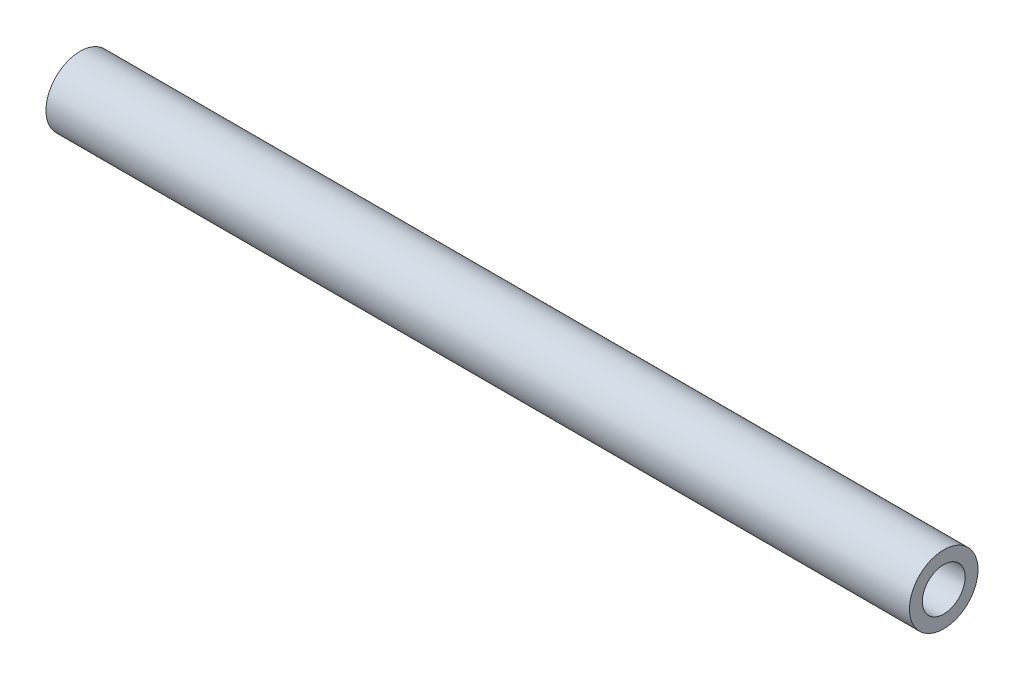
SolidWorks part; units mm, degrees
ref_plane "Front Plane" through (0, 0, 0) normal (0, 0, 1) x (1, 0, 0)
ref_plane "Top Plane" through (0, 0, 0) normal (0, 1, 0) x (1, 0, 0)
ref_plane "Right Plane" through (0, 0, 0) normal (1, 0, 0) x (0, 0, -1)
sketch "Sketch1" plane through (0, 0, 0) normal (1, 0, 0) x (0, 0, -1)
  circle A0 centre (0, 0) radius 3.175
  dimension "D1" = 6.35
extrude "Boss-Extrude1" add sketch "Sketch1" along normal blind 80.01
hole_wizard "5/32 (0.15625) Diameter Hole1" positions "Sketch2" profile "Sketch3" hole size "5/32" standard "ANSI Inch" end condition through all
sketch "Sketch2" plane through (0, 0, 0) normal (-1, 0, 0) x (0, 0, 1)
  point P0 (0, 0)
sketch "Sketch3" plane through (0, 0, 0) normal (0, 1, 0) x (0, 0, 1)
  line L0 (0, 0) -> (0, 80.01)
  line L1 (0, 80.01) -> (1.9844, 80.01)
  line L2 (1.9844, 80.01) -> (1.9844, 0)
  line L5 (1.9844, 0) -> (0, 0)
  line L11 (0, -6.35) -> (0, 107.95) construction
  dimension "Thru Hole Dia." = 3.9688
  dimension "Thru Hole Depth" = 80.01
